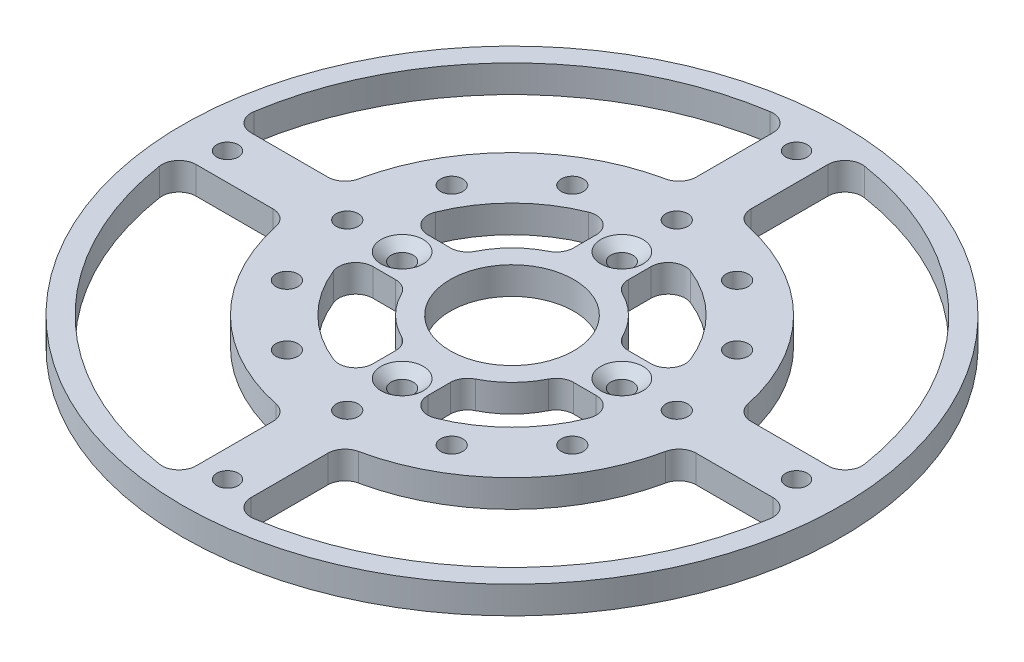
SolidWorks part; units mm, degrees
material "6061-T6 (SS)"
ref_plane "Front Plane" through (0, 0, 0) normal (0, 0, 1) x (1, 0, 0)
ref_plane "Top Plane" through (0, 0, 0) normal (0, 1, 0) x (1, 0, 0)
ref_plane "Right Plane" through (0, 0, 0) normal (1, 0, 0) x (0, 0, -1)
sketch "Sketch1" plane through (0, 0, 0) normal (0, 1, 0) x (1, 0, 0)
  circle A5 centre (0, 0) radius 76.2
  point P14 (0, 0)
  dimension "D4" = 152.4
extrude "Boss-Extrude1" add sketch "Sketch1" along normal blind 6.35
sketch "Sketch2" plane through (0, 6.35, 0) normal (0, 1, 0) x (1, 0, 0)
  circle A0 centre (0, 0) radius 14.2875
  dimension "D1" = 28.575
extrude "Cut-Extrude1" cut sketch "Sketch2" against normal through all
hole_wizard "CSK for #10 Flat Head Machine Screw (100)1" positions "Sketch5" profile "Sketch6" countersink size "#10" standard "ANSI Inch" end condition through all
sketch "Sketch5" plane through (0, 6.35, 0) normal (0, 1, 0) x (1, 0, 0)
  line L0 (0, 25.4) -> (0, 0) construction
  circle A0 centre (0, 0) radius 25.4
  point P0 (0, 25.4)
  point P13 (25.4, 0)
  point P15 (0, -25.4)
  point P17 (-25.4, 0)
  dimension "D1" = 50.8
sketch "Sketch6" plane through (0, 6.35, -25.4) normal (1, 0, 0) x (0, 0, 1)
  line L0 (0, 0) -> (0, 6.35)
  line L1 (0, 6.35) -> (2.5527, 6.35)
  line L2 (2.5527, 6.35) -> (2.5527, 1.9608)
  line L3 (2.5527, 1.9608) -> (4.8895, 0)
  line L5 (4.8895, 0) -> (0, 0)
  line L6 (-2.5527, 1.9608) -> (-4.8895, 0) construction
  line L11 (0, -6.35) -> (0, 107.95) construction
  dimension "Thru Hole Dia." = 5.1054
  dimension "Thru Hole Depth" = 6.35
  dimension "Near C'Sink Dia." = 9.779
  dimension "Near C'Sink Angle" = 100
hole_wizard "#9 (0.196) Diameter Hole1" positions "Sketch11" profile "Sketch10" hole size "#9" standard "ANSI Inch" end condition through all
sketch "Sketch11" plane through (0, 6.35, 0) normal (0, 1, 0) x (1, 0, 0)
  circle A0 centre (0, 0) radius 65.786
  point P0 (0, 65.786)
  point P9 (65.786, 0)
  point P11 (0, -65.786)
  point P13 (-65.786, 0)
  dimension "D1" = 131.572
sketch "Sketch10" plane through (0, 6.35, -65.786) normal (1, 0, 0) x (0, 0, 1)
  line L0 (0, 0) -> (0, 6.35)
  line L1 (0, 6.35) -> (2.4892, 6.35)
  line L2 (2.4892, 6.35) -> (2.4892, 0)
  line L5 (2.4892, 0) -> (0, 0)
  line L11 (0, -6.35) -> (0, 107.95) construction
  dimension "Thru Hole Dia." = 4.9784
  dimension "Thru Hole Depth" = 6.35
sketch "Sketch12" plane through (0, 6.35, 0) normal (0, 1, 0) x (1, 0, 0)
  line L0 (6.35, 48.93) -> (6.35, 66.675)
  line L1 (48.93, 6.35) -> (66.675, 6.35)
  line L2 (6.35, -48.93) -> (6.35, -66.675)
  line L3 (48.93, -6.35) -> (66.675, -6.35)
  line L4 (-48.93, -6.35) -> (-66.675, -6.35)
  line L5 (-6.35, -48.93) -> (-6.35, -66.675)
  line L6 (-6.35, 48.93) -> (-6.35, 66.675)
  line L7 (-48.93, 6.35) -> (-66.675, 6.35)
  arc A0 (9.4998, 45.0467) -> (45.0467, 9.4998) centre (0, 0) cw
  circle A1 centre (65.786, 0) radius 2.4892 construction
  circle A2 centre (0, 25.4) radius 2.5527 construction
  circle A3 centre (0, 0) radius 14.2875 construction
  arc A4 (10.9257, 70.5971) -> (70.5971, 10.9257) centre (0, 0) cw
  circle A5 centre (0, 0) radius 76.2 construction
  arc A6 (66.675, 6.35) -> (70.5971, 10.9257) centre (66.675, 10.3187) ccw
  arc A7 (45.0467, 9.4998) -> (48.93, 6.35) centre (48.93, 10.3187) ccw
  arc A8 (6.35, 48.93) -> (9.4998, 45.0467) centre (10.3188, 48.93) ccw
  arc A9 (6.35, 66.675) -> (10.9257, 70.5971) centre (10.3188, 66.675) cw
  arc A10 (9.4998, -45.0467) -> (6.35, -48.93) centre (10.3188, -48.93) ccw
  arc A11 (6.35, -66.675) -> (10.9257, -70.5971) centre (10.3188, -66.675) ccw
  arc A12 (70.5971, -10.9257) -> (10.9257, -70.5971) centre (0, 0) cw
  arc A13 (66.675, -6.35) -> (70.5971, -10.9257) centre (66.675, -10.3188) cw
  arc A14 (48.93, -6.35) -> (45.0467, -9.4998) centre (48.93, -10.3188) ccw
  arc A15 (45.0467, -9.4998) -> (9.4998, -45.0467) centre (0, 0) cw
  arc A16 (-45.0467, -9.4998) -> (-48.93, -6.35) centre (-48.93, -10.3187) ccw
  arc A17 (-66.675, -6.35) -> (-70.5971, -10.9257) centre (-66.675, -10.3188) ccw
  arc A18 (-10.9257, -70.5971) -> (-70.5971, -10.9257) centre (0, 0) cw
  arc A19 (-6.35, -66.675) -> (-10.9257, -70.5971) centre (-10.3187, -66.675) cw
  arc A20 (-6.35, -48.93) -> (-9.4998, -45.0467) centre (-10.3187, -48.93) ccw
  arc A21 (-9.4998, -45.0467) -> (-45.0467, -9.4998) centre (0, 0) cw
  arc A22 (-9.4998, 45.0467) -> (-6.35, 48.93) centre (-10.3188, 48.93) ccw
  arc A23 (-6.35, 66.675) -> (-10.9257, 70.5971) centre (-10.3188, 66.675) ccw
  arc A24 (-70.5971, 10.9257) -> (-10.9257, 70.5971) centre (0, 0) cw
  arc A25 (-66.675, 6.35) -> (-70.5971, 10.9257) centre (-66.675, 10.3188) cw
  arc A26 (-48.93, 6.35) -> (-45.0467, 9.4998) centre (-48.93, 10.3188) ccw
  arc A27 (-45.0467, 9.4998) -> (-9.4998, 45.0467) centre (0, 0) cw
  point P61 (0, 0)
  dimension "D1" = 6.35
  dimension "D3" = 31.75
  dimension "D4" = 4.7625
  dimension "D5" = 3.9688
  dimension "D2" = 6.35
  dimension "D6" = 4
extrude "Cut-Extrude2" cut sketch "Sketch12" against normal through all
hole_wizard "1/4-20 Tapped Hole1" positions "Sketch14" profile "Sketch15" tap size "1/4-20" standard "ANSI Inch" end condition through all
sketch "Sketch14" plane through (0, 6.35, 0) normal (0, 1, 0) x (1, 0, 0)
  line L0 (0, 0) -> (0, 38.1) construction
  line L1 (0, 0) -> (38.1, 0) construction
  circle A0 centre (0, 0) radius 38.1 construction
  point P0 (0, 38.1)
  point P12 (19.05, 32.9956)
  point P13 (32.9956, 19.05)
  point P14 (38.1, 0)
  point P15 (32.9956, -19.05)
  point P16 (19.05, -32.9956)
  point P17 (0, -38.1)
  point P18 (-19.05, -32.9956)
  point P19 (-32.9956, -19.05)
  point P20 (-38.1, 0)
  point P21 (-32.9956, 19.05)
  point P22 (-19.05, 32.9956)
  dimension "D1" = 38.1
  dimension "D2" = 12
sketch "Sketch15" plane through (0, 6.35, -38.1) normal (1, 0, 0) x (0, 0, 1)
  line L0 (0, 0) -> (0, 6.35)
  line L1 (0, 6.35) -> (2.5527, 6.35)
  line L2 (2.5527, 6.35) -> (2.5527, 0)
  line L5 (2.5527, 0) -> (0, 0)
  line L11 (0, -6.35) -> (0, 107.95) construction
  dimension "Thru Tap Drill Dia." = 5.1054
  dimension "Thru Tap Drill Depth" = 6.35
cosmetic thread "Hole Thread1" parameters "D2"=6.35
cosmetic thread "Hole Thread2" parameters "D2"=6.35
cosmetic thread "Hole Thread3" parameters "D2"=6.35
cosmetic thread "Hole Thread4" parameters "D2"=6.35
cosmetic thread "Hole Thread5" parameters "D2"=6.35
cosmetic thread "Hole Thread6" parameters "D2"=6.35
cosmetic thread "Hole Thread7" parameters "D2"=6.35
cosmetic thread "Hole Thread8" parameters "D2"=6.35
cosmetic thread "Hole Thread9" parameters "D2"=6.35
cosmetic thread "Hole Thread10" parameters "D2"=6.35
cosmetic thread "Hole Thread11" parameters "D2"=6.35
cosmetic thread "Hole Thread12" parameters "D2"=6.35
sketch "Sketch16" plane through (0, 6.35, 0) normal (0, 1, 0) x (1, 0, 0)
  line L0 (20.5764, 6.35) -> (25.7938, 6.35)
  line L1 (6.35, 20.5764) -> (6.35, 25.7938)
  line L2 (6.35, -20.5764) -> (6.35, -25.7938)
  line L3 (20.5764, -6.35) -> (25.7938, -6.35)
  line L4 (-20.5764, -6.35) -> (-25.7938, -6.35)
  line L5 (-6.35, -20.5764) -> (-6.35, -25.7938)
  line L6 (-6.35, 20.5764) -> (-6.35, 25.7938)
  line L7 (-20.5764, 6.35) -> (-25.7938, 6.35)
  arc A0 (8.5397, 17.0287) -> (17.0287, 8.5397) centre (0, 0) cw
  arc A1 (11.7929, 29.4787) -> (29.4787, 11.7929) centre (0, 0) cw
  circle A3 centre (0, 25.4) radius 2.5527 construction
  circle A4 centre (25.4, 0) radius 2.5527 construction
  circle A5 centre (0, 0) radius 14.2875 construction
  arc A6 (29.4787, 11.7929) -> (25.7938, 6.35) centre (25.7938, 10.3187) cw
  arc A7 (17.0287, 8.5397) -> (20.5764, 6.35) centre (20.5764, 10.3187) ccw
  arc A8 (8.5397, 17.0287) -> (6.35, 20.5764) centre (10.3187, 20.5764) cw
  arc A9 (6.35, 25.7938) -> (11.7929, 29.4787) centre (10.3187, 25.7938) cw
  arc A10 (8.5397, -17.0287) -> (6.35, -20.5764) centre (10.3187, -20.5764) ccw
  arc A11 (11.7929, -29.4787) -> (6.35, -25.7938) centre (10.3187, -25.7938) cw
  arc A12 (29.4787, -11.7929) -> (11.7929, -29.4787) centre (0, 0) cw
  arc A13 (25.7938, -6.35) -> (29.4787, -11.7929) centre (25.7938, -10.3188) cw
  arc A14 (17.0287, -8.5397) -> (20.5764, -6.35) centre (20.5764, -10.3188) cw
  arc A15 (17.0287, -8.5397) -> (8.5397, -17.0287) centre (0, 0) cw
  arc A16 (-17.0287, -8.5397) -> (-20.5764, -6.35) centre (-20.5764, -10.3187) ccw
  arc A17 (-29.4787, -11.7929) -> (-25.7938, -6.35) centre (-25.7938, -10.3187) cw
  arc A18 (-11.7929, -29.4787) -> (-29.4787, -11.7929) centre (0, 0) cw
  arc A19 (-6.35, -25.7938) -> (-11.7929, -29.4787) centre (-10.3188, -25.7938) cw
  arc A20 (-8.5397, -17.0287) -> (-6.35, -20.5764) centre (-10.3188, -20.5764) cw
  arc A21 (-8.5397, -17.0287) -> (-17.0287, -8.5397) centre (0, 0) cw
  arc A22 (-8.5397, 17.0287) -> (-6.35, 20.5764) centre (-10.3187, 20.5764) ccw
  arc A23 (-11.7929, 29.4787) -> (-6.35, 25.7938) centre (-10.3187, 25.7938) cw
  arc A24 (-29.4787, 11.7929) -> (-11.7929, 29.4787) centre (0, 0) cw
  arc A25 (-25.7938, 6.35) -> (-29.4787, 11.7929) centre (-25.7938, 10.3188) cw
  arc A26 (-17.0287, 8.5397) -> (-20.5764, 6.35) centre (-20.5764, 10.3188) cw
  arc A27 (-17.0287, 8.5397) -> (-8.5397, 17.0287) centre (0, 0) cw
  point P59 (0, 0)
  dimension "D1" = 31.75
  dimension "D4" = 4.7625
  dimension "D5" = 3.9688
  dimension "D2" = 6.35
  dimension "D3" = 6.35
  dimension "D6" = 4
extrude "Cut-Extrude3" cut sketch "Sketch16" against normal blind 6.35
